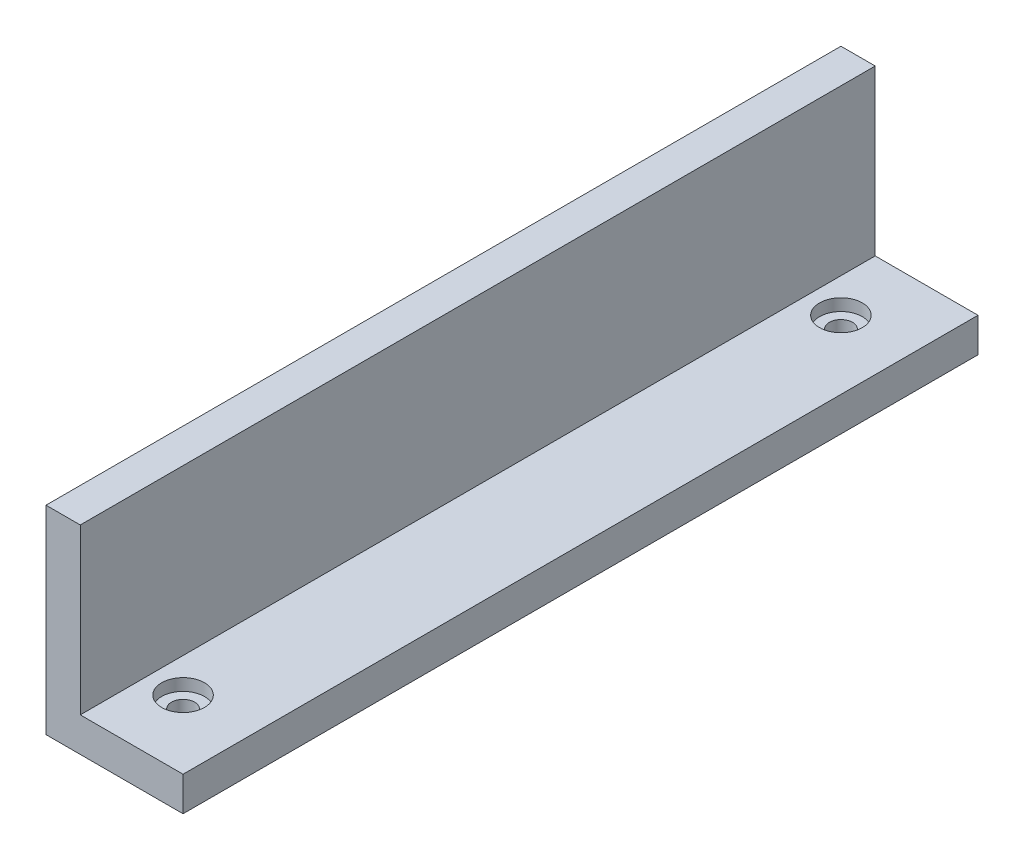
SolidWorks part; units mm, degrees
ref_plane "Front Plane" through (0, 0, 0) normal (0, 0, 1) x (1, 0, 0)
ref_plane "Top Plane" through (0, 0, 0) normal (0, 1, 0) x (1, 0, 0)
ref_plane "Right Plane" through (0, 0, 0) normal (1, 0, 0) x (0, 0, -1)
sketch "Sketch1" plane through (0, 0, 0) normal (0, 1, 0) x (1, 0, 0)
  line L1 (0, 0) -> (25.4, 0)
  line L2 (0, 0) -> (0, 147.32)
  line L3 (0, 147.32) -> (25.4, 147.32)
  line L4 (25.4, 0) -> (25.4, 147.32)
  dimension "D1" = 147.32
  dimension "D2" = 25.4
extrude "Boss-Extrude1" add sketch "Sketch1" against normal blind 6.35
sketch "Sketch2" plane through (0, 0, 0) normal (-1, 0, 0) x (0, 0, 1)
  line L1 (0, 0) -> (-147.32, 0)
  line L2 (0, 0) -> (0, 30.48)
  line L3 (0, 30.48) -> (-147.32, 30.48)
  line L4 (-147.32, 0) -> (-147.32, 30.48)
  line L5 (-147.32, -6.35) -> (-147.32, 0) construction
  dimension "D1" = 30.48
extrude "Boss-Extrude2" add sketch "Sketch2" against normal blind 6.35
sketch "Sketch5" plane through (0, 0, 0) normal (0, 1, 0) x (1, 0, 0)
  line L0 (12.7, 0) -> (12.7, 147.32)
  line L1 (6.35, 0) -> (25.4, 0) construction
  line L2 (25.4, 147.32) -> (6.35, 147.32) construction
  line L3 (0, 0) -> (25.4, 0) construction
  point P9 (12.7, 12.7)
  point P11 (12.7, 134.62)
  dimension "D1" = 12.7
  dimension "D2" = 121.92
hole_wizard "CBORE for #6 Binding Head Machine Screw1" positions "Sketch7" profile "Sketch8" counterbore size "#6" standard "ANSI Inch" end condition up to next
sketch "Sketch7" plane through (0, 0, 0) normal (0, 1, 0) x (1, 0, 0)
  point P0 (12.7, 12.7)
  point P3 (12.7, 134.62)
sketch "Sketch8" plane through (12.7, 0, -12.7) normal (1, 0, 0) x (0, 0, 1)
  line L0 (0, 0) -> (0, 6.35)
  line L1 (0, 6.35) -> (2.1526, 6.35)
  line L3 (2.1526, 6.35) -> (2.1527, 2.2098)
  line L4 (2.1527, 2.2098) -> (3.9687, 2.2098)
  line L5 (3.9687, 2.2098) -> (3.9687, 0)
  line L7 (3.9687, 0) -> (0, 0)
  line L11 (0, -6.35) -> (0, 107.95) construction
  dimension "Thru Hole Dia." = 4.3053
  dimension "Thru Hole Depth" = 6.35
  dimension "C'Bore Dia." = 7.9375
  dimension "C'Bore Depth" = 2.2098
sketch "Sketch9" plane through (6.35, 0, 0) normal (1, 0, 0) x (0, 0, -1)
  line L0 (12.7, 15.24) -> (134.62, 15.24) construction
  line L2 (12.7, 22.4937) -> (134.62, 22.4937)
  line L3 (12.7, 7.9863) -> (134.62, 7.9863)
  line L5 (0, 0) -> (0, 30.48) construction
  line L6 (147.32, 30.48) -> (147.32, 0) construction
  line L7 (0, 30.48) -> (147.32, 30.48) construction
  line L8 (147.32, 0) -> (0, 0) construction
  arc A0 (12.7, 22.4937) -> (12.7, 7.9863) centre (12.7, 15.24) ccw
  arc A1 (134.62, 7.9863) -> (134.62, 22.4937) centre (134.62, 15.24) ccw
  point P4 (73.66, 15.24)
  point P9 (7.4347, 15.1883)
  dimension "D1" = 12.7
  dimension "D2" = 12.7
  dimension "D3" = 14.5075
